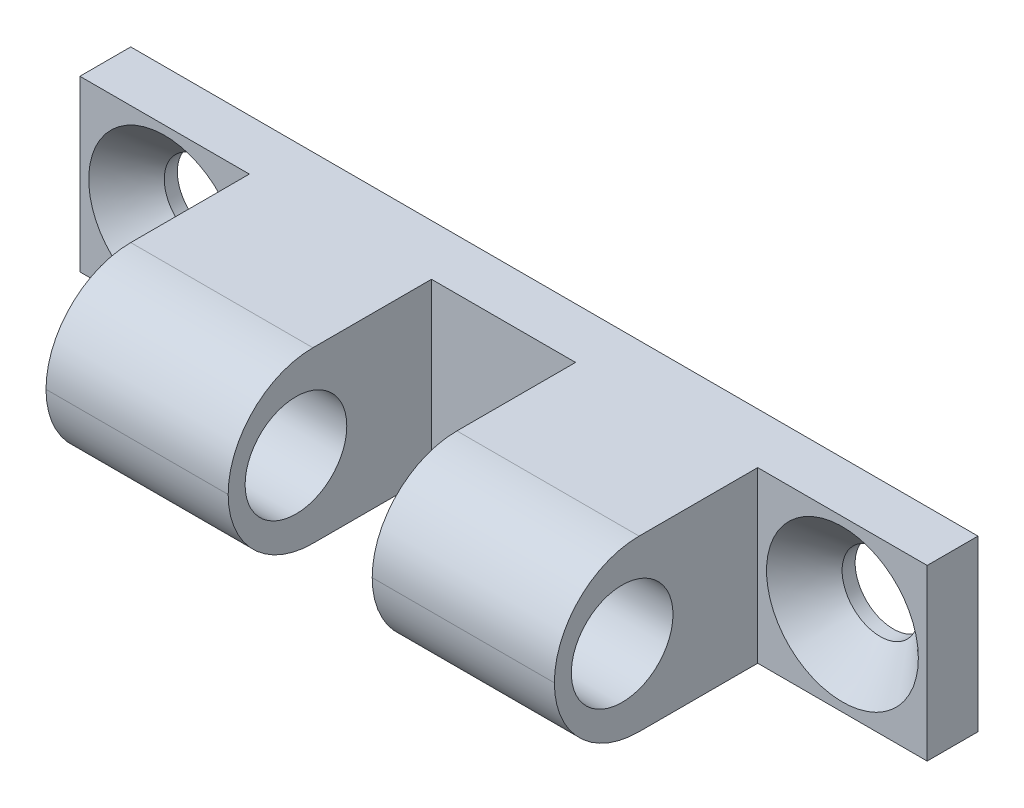
SolidWorks part; units mm, degrees
ref_plane "前视基准面" through (0, 0, 0) normal (0, 0, 1) x (1, 0, 0)
ref_plane "上视基准面" through (0, 0, 0) normal (0, 1, 0) x (1, 0, 0)
ref_plane "右视基准面" through (0, 0, 0) normal (1, 0, 0) x (0, 0, -1)
sketch "草图1" plane through (0, 0, 0) normal (0, 1, 0) x (1, 0, 0)
  line L0 (4.25, -15) -> (15, -15)
  line L1 (-25, 0) -> (25, 0)
  line L2 (-25, 0) -> (-25, -3)
  line L3 (-25, -3) -> (-15, -3)
  line L4 (25, 0) -> (25, -3)
  line L5 (-4.25, -3) -> (4.25, -3)
  line L6 (-15, -3) -> (-15, -15)
  line L7 (-15, -15) -> (-4.25, -15)
  line L8 (15, -3) -> (15, -15)
  line L9 (-4.25, -3) -> (4.25, -3)
  line L10 (-4.25, -15) -> (-4.25, -3)
  line L12 (4.25, -15) -> (4.25, -3)
  line L13 (15, -3) -> (25, -3)
  dimension "D1" = 50
  dimension "D2" = 30
  dimension "D3" = 8.5
  dimension "D4" = 10
  dimension "D5" = 3
  dimension "D6" = 15
extrude "拉伸1" add sketch "草图1" along normal mid plane 10 contours L8 L13 L4 L1 L2 L6 L10 L12 L0 region at (4.772, 0, 9)
hole_wizard "M4 六角凹锥坑螺钉的锥形沉头孔1" positions "3D草图1" profile "草图2" countersink size "M4" standard "ISO" end condition through all
sketch3d "3D草图1"
  point P0 (-20, 0, 3)
  point P2 (20, 0, 3)
sketch "草图2" plane through (-20, 0, 3) normal (1, 0, 0) x (0, -1, 0)
  line L0 (0, 0) -> (0, 3)
  line L1 (0, 3) -> (2.25, 3)
  line L2 (2.25, 3) -> (2.25, 2.23)
  line L3 (2.25, 2.23) -> (4.48, 0)
  line L5 (4.48, 0) -> (0, 0)
  line L6 (-2.25, 2.23) -> (-4.48, 0) construction
  line L11 (0, -6.35) -> (0, 107.95) construction
  dimension "通孔孔直径" = 4.5
  dimension "通孔孔深度" = 3
  dimension "近端锥形沉头孔直径" = 8.96
  dimension "近端锥形沉头孔角度" = 90
sketch "草图3" plane through (15, 0, 0) normal (1, 0, 0) x (0, 0, -1)
  line L0 (-15, 5) -> (-15, -5) construction
  circle A0 centre (-11, 0) radius 3
  dimension "D1" = 4
extrude "拉伸2" cut sketch "草图3" against normal through all
fillet "圆角1" radius 5 4 edges at (-9.625, -5, 15) (9.625, -5, 15) (9.625, 5, 15) (-9.625, 5, 15)
